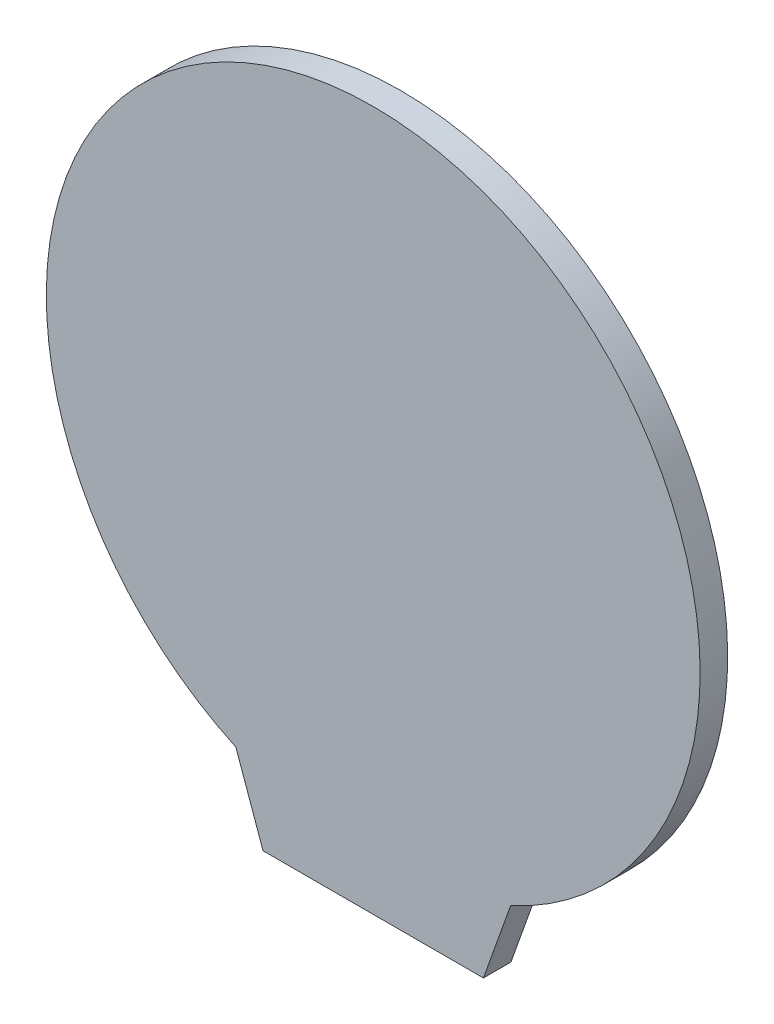
SolidWorks part; units mm, degrees
ref_plane "前视基准面" through (0, 0, 0) normal (0, 0, 1) x (1, 0, 0)
ref_plane "上视基准面" through (0, 0, 0) normal (0, 1, 0) x (1, 0, 0)
ref_plane "右视基准面" through (0, 0, 0) normal (1, 0, 0) x (0, 0, -1)
sketch "草图2" plane through (0, 0, 0) normal (0, 0, 1) x (1, 0, 0)
  line L1 (-6, -20.3) -> (6, -20.3)
  line L2 (6, -20.3) -> (7.4798, -16.1522)
  line L3 (-6, -20.3) -> (-7.4798, -16.1522)
  arc A0 (7.4798, -16.1522) -> (-7.4798, -16.1522) centre (0, 0) ccw
extrude "凸台-拉伸1" add sketch "草图2" along normal blind 1.5
